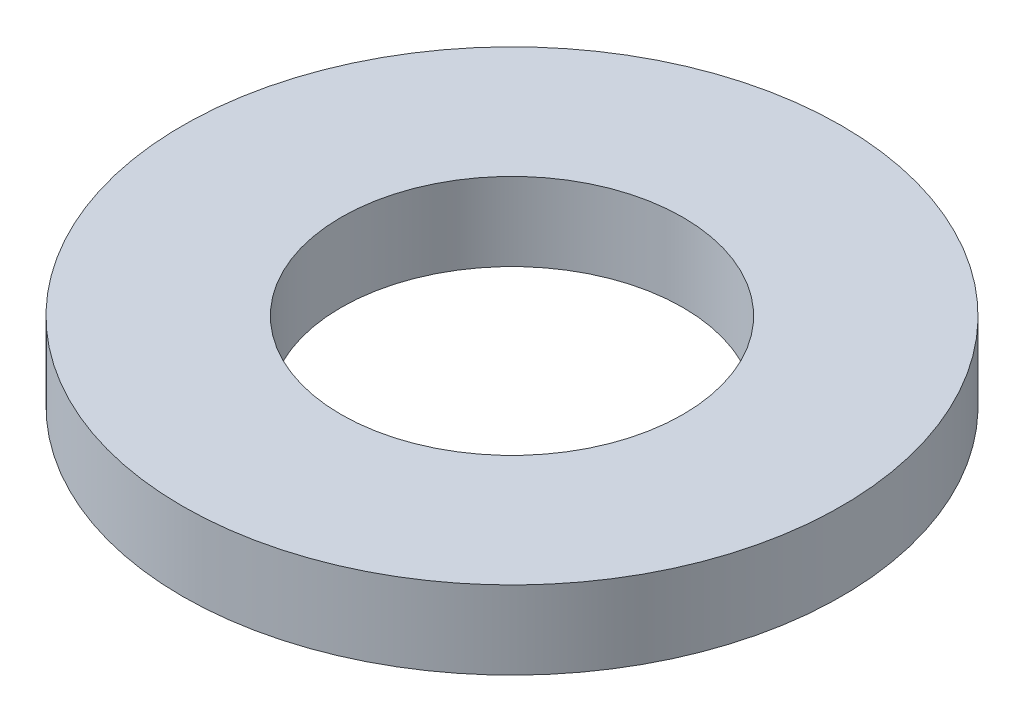
SolidWorks part; units mm, degrees
ref_plane "Front Plane" through (0, 0, 0) normal (0, 0, 1) x (1, 0, 0)
ref_plane "Top Plane" through (0, 0, 0) normal (0, 1, 0) x (1, 0, 0)
ref_plane "Right Plane" through (0, 0, 0) normal (1, 0, 0) x (0, 0, -1)
sketch "Sketch1" plane through (0, 0, 0) normal (0, 1, 0) x (1, 0, 0)
  circle A0 centre (0, 0) radius 67.5
  dimension "FLANGE_OD" = 135
extrude "Boss-Extrude1" add sketch "Sketch1" along normal blind 16
sketch "Sketch2" plane through (0, 0, 0) normal (0, 1, 0) x (1, 0, 0)
  circle A0 centre (0, 0) radius 35
  dimension "BORE_D" = 70
extrude "Cut-Extrude1" cut sketch "Sketch2" along normal through all
sketch "Sketch3" plane through (0, 16, 0) normal (0, 1, 0) x (1, 0, 0)
  circle A0 centre (0, 0) radius 21.7067 construction
  circle A1 centre (-21.7067, 0) radius 3.8329
  dimension "BOLT_D" = 7.6658
  dimension "BOLT_PCD" = 43.4134
extrude "Cut-Extrude2" cut sketch "Sketch3" against normal blind 12.6633 rebuild error yes
pattern_circular "CirPattern1" count 8 over 360 rebuild error yes
